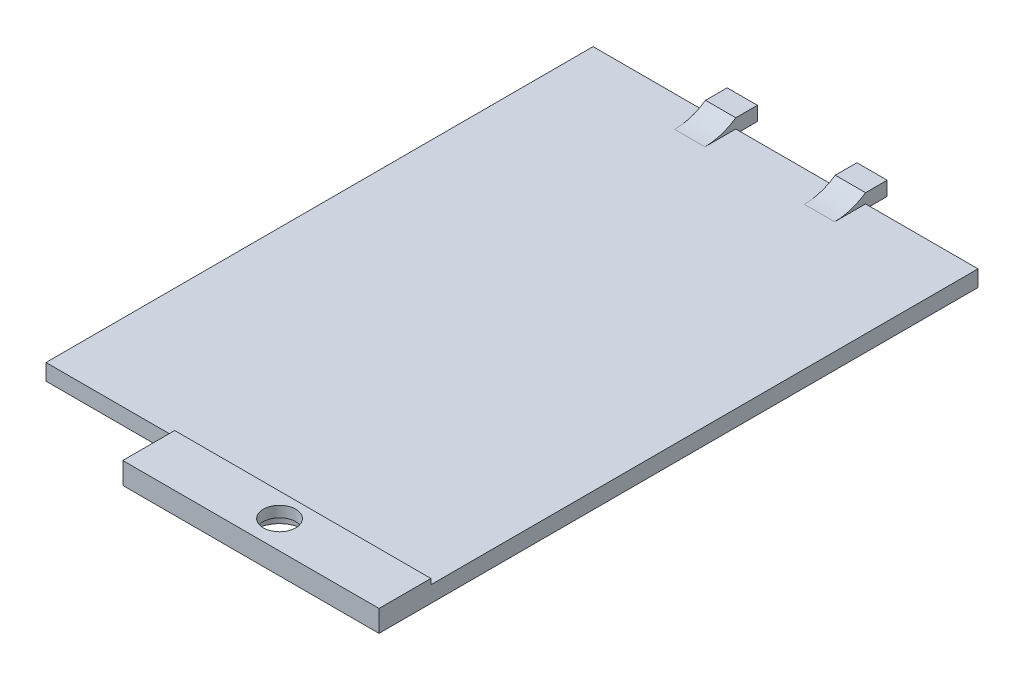
SolidWorks part; units mm, degrees
ref_plane "前视基准面" through (0, 0, 0) normal (0, 0, 1) x (1, 0, 0)
ref_plane "上视基准面" through (0, 0, 0) normal (0, 1, 0) x (1, 0, 0)
ref_plane "右视基准面" through (0, 0, 0) normal (1, 0, 0) x (0, 0, -1)
other "Configuration Table"
sketch "草图1" plane through (0, 0, 0) normal (0, 1, 0) x (1, 0, 0)
  line L1 (0, -50.6) -> (35.6, -50.6)
  line L2 (0, -50.6) -> (0, 0)
  line L3 (0, 0) -> (35.6, 0)
  line L4 (35.6, -50.6) -> (35.6, 0)
  dimension "D1" = 35.6
  dimension "D2" = 50.6
extrude "凸台-拉伸1" add sketch "草图1" along normal blind 1.5
sketch "草图2" plane through (0, 0, 0) normal (0, -1, 0) x (1, 0, 0)
  line L0 (0, 50.6) -> (35.6, 50.6) construction
  line L1 (11.9, 50.6) -> (35.6, 50.6)
  line L2 (11.9, 50.6) -> (11.9, 55.4)
  line L3 (11.9, 55.4) -> (35.6, 55.4)
  line L4 (35.6, 50.6) -> (35.6, 55.4)
  line L5 (35.6, 50.6) -> (35.6, 0) construction
  circle A0 centre (23.8, 52.8) radius 1.5
  circle A1 centre (23.8, 52.8) radius 2.25
  point P9 (23.8, 53.8)
  point P11 (0, 0)
  point P14 (23.7687, 52.8363)
  point P17 (0, 0)
  dimension "D1" = 3
  dimension "D2" = 4.5
  dimension "D3" = 4.8
  dimension "D4" = 23.7
extrude "凸台-拉伸2" add sketch "草图2" against normal blind 2 contours L4 L3 L2 L1 | A0
extrude "切除-拉伸1" cut sketch "草图2<3>" against normal blind 1 contours A1
sketch "草图2<3>" plane through (0, 0, 0) normal (0, -1, 0) x (1, 0, 0) same geometry as "草图2"
sketch "草图3" plane through (0, 0, 0) normal (0, 0, -1) x (-1, 0, 0)
  line L0 (-35.6, 0) -> (0, 0) construction
  line L1 (-25.2, 1.1) -> (-22.4, 1.1)
  line L2 (-25.2, 1.1) -> (-25.2, 2.4)
  line L3 (-25.2, 2.4) -> (-22.4, 2.4)
  line L4 (-22.4, 1.1) -> (-22.4, 2.4)
  line L5 (-13.2, 1.1) -> (-10.4, 1.1)
  line L6 (-13.2, 1.1) -> (-13.2, 2.4)
  line L7 (-13.2, 2.4) -> (-10.4, 2.4)
  line L8 (-10.4, 1.1) -> (-10.4, 2.4)
  line L9 (-35.6, 1.5) -> (-35.6, 0) construction
  dimension "D1" = 1.1
  dimension "D2" = 1.3
  dimension "D3" = 2.8
  dimension "D4" = 10.4
  dimension "D5" = 9.2
extrude "凸台-拉伸3" add sketch "草图3" along normal blind 2 contours L2 L3 L4 L1 | L6 L7 L8 L5
fillet "圆角1" radius 5 2 edges at (11.8, 1.5, 0) (23.8, 1.5, 0)
